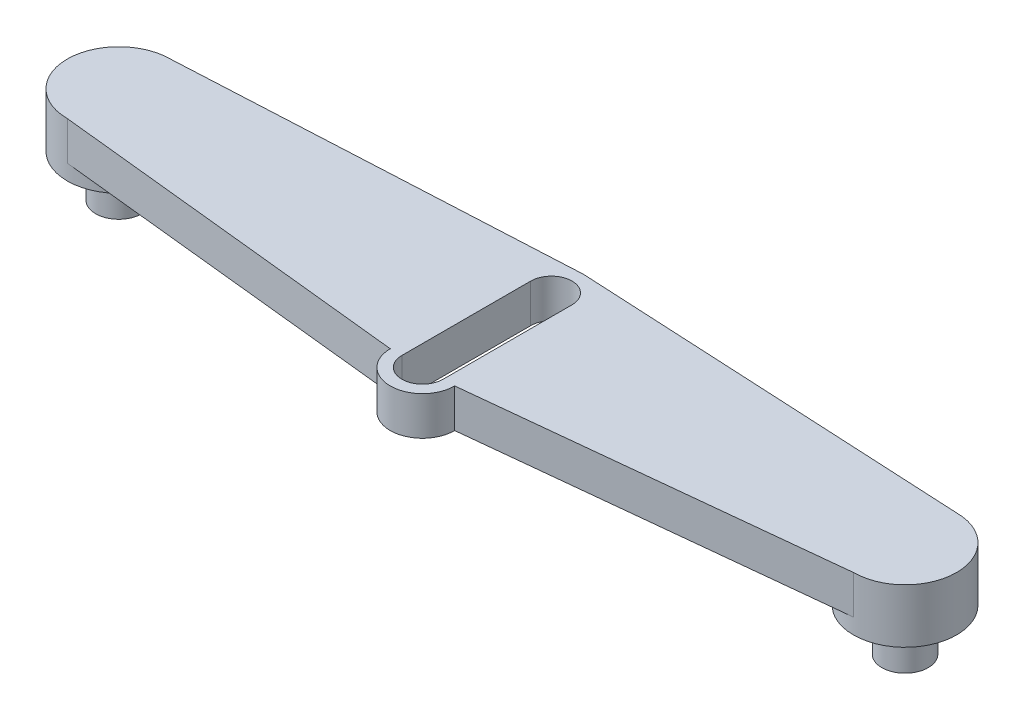
SolidWorks part; units mm, degrees
ref_plane "Front Plane" through (0, 0, 0) normal (0, 0, 1) x (1, 0, 0)
ref_plane "Top Plane" through (0, 0, 0) normal (0, 1, 0) x (1, 0, 0)
ref_plane "Right Plane" through (0, 0, 0) normal (1, 0, 0) x (0, 0, -1)
sketch "Sketch1" plane through (0, 0, 0) normal (0, 1, 0) x (1, 0, 0)
  line L0 (36.7994, -18.835) -> (36.7994, -8.835) construction
  line L1 (35.1994, -18.835) -> (35.1994, -8.835)
  line L2 (38.3994, -18.835) -> (38.3994, -8.835)
  line L3 (36.7994, -18.835) -> (36.7994, -8.835) construction
  line L4 (34.2994, -18.835) -> (34.2994, -8.835)
  line L5 (39.2994, -18.835) -> (39.2994, -8.835)
  line L6 (6.2994, -7.8978) -> (36.7994, -6.335)
  line L7 (36.7994, -6.335) -> (67.3024, -7.894)
  line L8 (6.2994, -15.8952) -> (34.2994, -18.835)
  line L9 (39.2994, -18.835) -> (67.3024, -15.899)
  circle A1 centre (67.3024, -11.8965) radius 2
  arc A2 (34.2994, -18.835) -> (39.2994, -18.835) centre (36.7994, -18.835) ccw
  circle A4 centre (67.3024, -11.8965) radius 1.8
  arc A5 (35.1994, -18.835) -> (38.3994, -18.835) centre (36.7994, -18.835) ccw
  arc A6 (38.3994, -8.835) -> (35.1994, -8.835) centre (36.7994, -8.835) ccw
  arc A7 (39.2994, -8.835) -> (34.2994, -8.835) centre (36.7994, -8.835) ccw
  circle A8 centre (67.3024, -11.8965) radius 4.0025
  circle A9 centre (6.2994, -11.8965) radius 2
  circle A10 centre (6.2994, -11.8965) radius 1.8
  circle A11 centre (6.2994, -11.8965) radius 3.9987
  point P3 (67.454, -7.9407)
  point P4 (36.7994, -13.835)
  point P5 (6.451, -7.9407)
  point P13 (36.7994, -13.835)
  point P21 (6.451, -7.8978)
  point P22 (36.7994, -6.335)
  point P23 (6.4525, -7.9337)
  point P24 (6.451, -7.8978)
  point P35 (36.951, -9.3569)
  point P36 (36.951, -18.835)
  point P37 (36.9963, -18.835)
  point P38 (36.8446, -11.2525)
  point P39 (36.8067, -6.1722)
  point P40 (36.8446, -8.3332)
  dimension "D1" = 30.503
  dimension "D3" = 30.5
extrude "Boss-Extrude1" add sketch "Sketch1" along normal blind 3 contours A11 A2 L4 A7 | L5 A7 L4 A2 A6 L2 A5 L1 | A8 A7 L5 A2 | A8 A1 | A1 A4 | A4 | A11 region at (22.642, 0, 12.3143) region at (34.4575, 0, 13.835) region at (50.9585, 0, 12.3142) region at (63.4131, 0, 11.8965) region at (65.3589, 0, 11.8965) region at (67.3024, 0, 11.8965)
extrude "Boss-Extrude2" add sketch "Sketch1<3>" against normal blind 4.5 contours A10 | A4 region at (67.3024, 0, 11.8965) region at (6.2994, 0, 11.8965)
sketch "Sketch1<3>" plane through (0, 0, 0) normal (0, 1, 0) x (1, 0, 0) same geometry as "Sketch1"
extrude "Boss-Extrude3" add sketch "Sketch1<4>" against normal blind 1.2 contours A11 A9 | A8 A1 region at (2.4138, 0, 11.8965) region at (63.4131, 0, 11.8965)
sketch "Sketch1<4>" plane through (0, 0, 0) normal (0, 1, 0) x (1, 0, 0) same geometry as "Sketch1"
